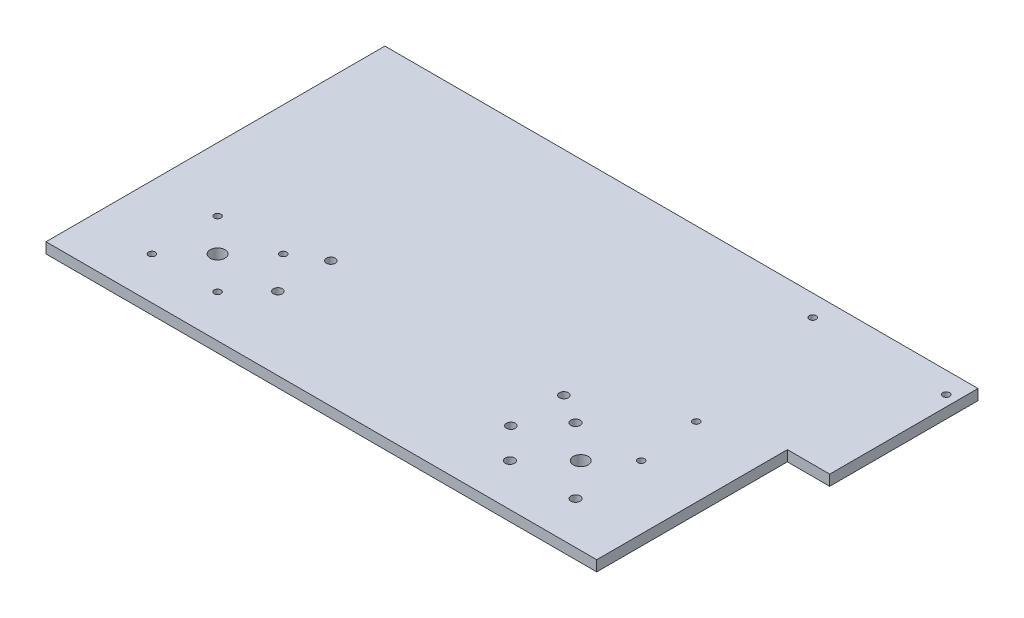
SolidWorks part; units mm, degrees
ref_plane "前视基准面" through (0, 0, 0) normal (0, 0, 1) x (1, 0, 0)
ref_plane "上视基准面" through (0, 0, 0) normal (0, 1, 0) x (1, 0, 0)
ref_plane "右视基准面" through (0, 0, 0) normal (1, 0, 0) x (0, 0, -1)
sketch "草图1" plane through (0, 0, 0) normal (0, 1, 0) x (1, 0, 0)
  line L0 (-79, -60) -> (-110, -60) construction
  line L1 (-140, -80) -> (140, -80)
  line L2 (-140, -80) -> (-140, 80)
  line L3 (-140, 80) -> (140, 80)
  line L4 (140, -80) -> (140, 80)
  line L5 (-140, -80) -> (140, 80) construction
  line L6 (-140, 80) -> (140, -80) construction
  line L7 (140, -80) -> (120, -80)
  line L8 (140, -80) -> (140, 10)
  line L9 (140, 10) -> (120, 10)
  line L10 (120, -80) -> (120, 10)
  line L11 (90, -60) -> (59, -60) construction
  line L12 (90, -60) -> (90, -29) construction
  line L13 (90, -29) -> (59, -29) construction
  line L14 (59, -60) -> (59, -29) construction
  line L15 (90, -60) -> (59, -29) construction
  line L16 (90, -29) -> (59, -60) construction
  line L17 (-79, -60) -> (-79, -29) construction
  line L18 (-79, -29) -> (-110, -29) construction
  line L19 (-110, -60) -> (-110, -29) construction
  line L20 (-79, -60) -> (-110, -29) construction
  line L21 (-79, -29) -> (-110, -60) construction
  line L23 (45, -20.5) -> (-65, -20.5) construction
  line L24 (45, -20.5) -> (45, -45.5) construction
  line L25 (45, -45.5) -> (-65, -45.5) construction
  line L26 (-65, -20.5) -> (-65, -45.5) construction
  circle A0 centre (90, -29) radius 1.6
  circle A1 centre (59, -29) radius 2.2
  circle A2 centre (90, -60) radius 2.2
  circle A3 centre (59, -60) radius 2.2
  circle A4 centre (-79, -29) radius 1.6
  circle A5 centre (-110, -29) radius 1.6
  circle A6 centre (-79, -60) radius 1.6
  circle A7 centre (-110, -60) radius 1.6
  circle A8 centre (45, -20.5) radius 2.1
  circle A9 centre (45, -45.5) radius 2.1
  circle A10 centre (-65, -45.5) radius 2.1
  circle A11 centre (-65, -20.5) radius 2.1
  circle A14 centre (75.7273, -43.2727) radius 3.5
  circle A15 centre (-94.5, -44.5) radius 3.5
  circle A19 centre (87, 0) radius 1.6
  circle A20 centre (72, 70) radius 1.6
  circle A21 centre (135, 70) radius 1.6
  point P0 (0, 0)
  point P9 (0, 0)
  point P30 (0, 0)
  point P31 (0, 0)
  point P42 (0, 0)
  point P44 (0, 0)
  point P46 (66.9093, -42.0372)
  point P50 (80.5708, -31.804)
  point P51 (75.7476, -43.2956)
  point P52 (75.7264, -43.2722)
  point P53 (75.0855, -42.906)
  point P54 (75.7184, -43.2676)
  point P55 (75.7273, -43.2727)
  dimension "D9" = 3.2
  dimension "D10" = 4.4
  dimension "D11" = 4.4
  dimension "D12" = 4.4
  dimension "D17" = 3.2
  dimension "D18" = 3.2
  dimension "D19" = 3.2
  dimension "D20" = 3.2
  dimension "D25" = 4.2
  dimension "D26" = 4.2
  dimension "D27" = 4.2
  dimension "D28" = 4.2
  dimension "D29" = 7
  dimension "D30" = 7
  dimension "D34" = 68
  dimension "D35" = 53
  dimension "D36" = 80
  dimension "D37" = 3.2
  dimension "D38" = 3.2
  dimension "D39" = 3.2
  dimension "D1" = 280
  dimension "D2" = 160
  dimension "D3" = 20
  dimension "D4" = 90
  dimension "D5" = 31
  dimension "D6" = 31
  dimension "D7" = 20
  dimension "D8" = 50
  dimension "D13" = 31
  dimension "D14" = 31
  dimension "D15" = 20
  dimension "D16" = 30
  dimension "D21" = 110
  dimension "D22" = 34.5
  dimension "D23" = 14
  dimension "D24" = 25
  dimension "D31" = 5
  dimension "D32" = 10
  dimension "D33" = 10
extrude "凸台-拉伸1" add sketch "草图1" along normal blind 5 contours L1 L10 L9 L4 L3 L2 region at (-5.5179, 0, -1.6608)
